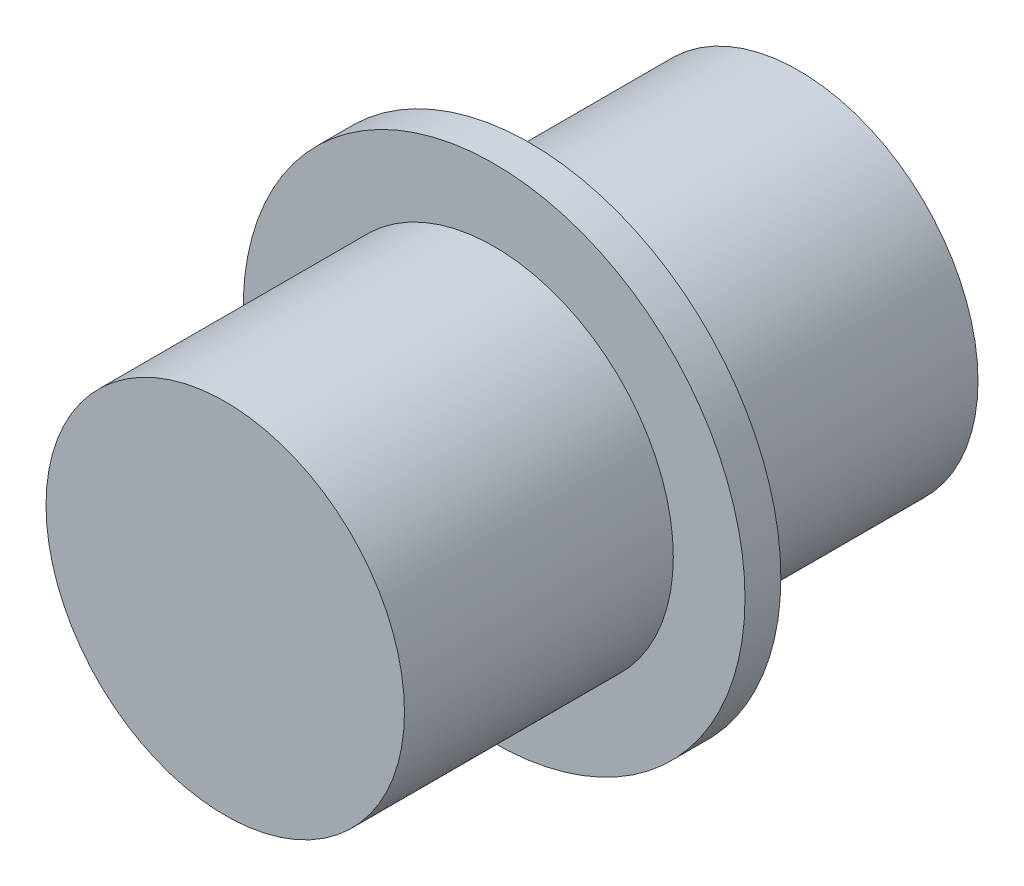
SolidWorks part; units mm, degrees
ref_plane "Front Plane" through (0, 0, 0) normal (0, 0, 1) x (1, 0, 0)
ref_plane "Top Plane" through (0, 0, 0) normal (0, 1, 0) x (1, 0, 0)
ref_plane "Right Plane" through (0, 0, 0) normal (1, 0, 0) x (0, 0, -1)
sketch "Sketch1" plane through (0, 0, 0) normal (0, 0, 1) x (1, 0, 0)
  circle A0 centre (0, 0) radius 10
  dimension "D1" = 20
extrude "Boss-Extrude1" add sketch "Sketch1" along normal blind 15
sketch "Sketch2" plane through (0, 0, 15) normal (0, 0, 1) x (1, 0, 0)
  circle A0 centre (0, 0) radius 14
  circle A1 centre (0, 0) radius 10 construction
  dimension "D1" = 4
extrude "Boss-Extrude2" add sketch "Sketch2" along normal blind 2
sketch "Sketch3" plane through (0, 0, 17) normal (0, 0, 1) x (1, 0, 0)
  circle A0 centre (0, 0) radius 10
  dimension "D1" = 20
extrude "Boss-Extrude4" add sketch "Sketch3" along normal blind 15
